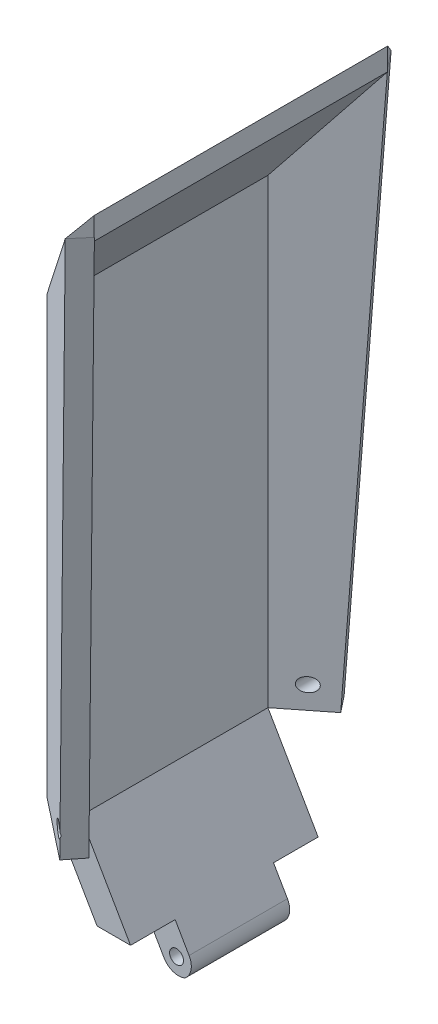
SolidWorks part; units mm, degrees
ref_plane "Front Plane" through (0, 0, 0) normal (0, 0, 1) x (1, 0, 0)
ref_plane "Top Plane" through (0, 0, 0) normal (0, 1, 0) x (1, 0, 0)
ref_plane "Right Plane" through (0, 0, 0) normal (1, 0, 0) x (0, 0, -1)
sketch "Sketch1" plane through (0, 0, 0) normal (0, 1, 0) x (1, 0, 0)
  line L4 (0, 0) -> (0, 16.82)
  line L5 (0, 16.82) -> (7.8551, 23.0085)
  line L6 (7.8551, 23.0085) -> (9.004, 21.5502)
  line L7 (9.004, 21.5502) -> (3, 16.82)
  line L8 (3, 16.82) -> (3, 0)
  line L9 (3, 0) -> (8.9971, -4.739)
  line L10 (8.9971, -4.739) -> (7.846, -6.2)
  line L11 (7.846, -6.2) -> (0, 0)
  point P2 (3, 16.82)
  point P3 (0, 0)
  point P11 (0, 0)
  point P12 (0, 0)
  dimension "D1" = 16.82
  dimension "D2" = 10
  dimension "D3" = 10
  dimension "D4" = 3
  dimension "D5" = 1.86
  dimension "D6" = 1.8566
extrude "Boss-Extrude1" add sketch "Sketch1" along normal blind 50
sketch "Sketch8" plane through (0, 0, 0) normal (0, 0, 1) x (1, 0, 0)
  line L0 (0, 0) -> (5.9985, -10.3896) construction
  line L2 (0, 50) -> (0, 0) construction
  line L3 (3, 0) -> (7, 0) construction
  point P8 (8.9971, 0)
  dimension "D1" = 150
  dimension "3.5" = 4
sketch "Sketch2" plane through (0, 0, 0) normal (-0.62, 0, 0.7846) x (0.7846, 0, 0.62)
  line L0 (11.46, 50) -> (0, 37)
  line L1 (0, 50) -> (0, 0) construction
  line L2 (0, 37) -> (0, 50)
  line L3 (0, 50) -> (11.46, 50)
  point P5 (10.6574, 50)
  point P8 (11.4137, 50)
  point P10 (0, 0)
  dimension "D1" = 13
  dimension "D2" = 11.46
extrude "Cut-Extrude1" cut sketch "Sketch2" along direction (0, 0, 1) on the side against the normal blind 30
sketch "Sketch5" plane through (-17.3103, 11.9728, 0) normal (-0.8224, 0.5688, 0) x (0, 0, 1)
  line L0 (0, 30.4304) -> (6.2, 44.2232)
  line L1 (6.2, 44.2232) -> (4.746, 46.2369)
  line L5 (-21.566, 46.2369) -> (-23.0085, 44.2391)
  line L6 (-23.0085, 44.2391) -> (-16.82, 30.4304)
  line L7 (-16.82, 30.4304) -> (0, 30.4304)
  line L8 (-21.566, 46.2369) -> (4.746, 46.2369)
  point P4 (0, 0)
  point P7 (-21.566, 46.2369)
extrude "Boss-Extrude2" add sketch "Sketch5" along direction (0, -1, 0) on the side of the normal blind 2 contours L8 L1 L0 L7 L6 L5
sketch "Sketch6" plane through (0, 0, 0) normal (-0.62, 0, 0.7846) x (0.7846, 0, 0.62)
  line L0 (10, 50.3438) -> (7, 0)
  line L2 (7, 0) -> (10, 0)
  line L3 (10, 0) -> (10, 50.3438)
  point P3 (6.2396, 0)
  point P5 (0, 0)
  dimension "D1" = 3
extrude "Cut-Extrude2" cut sketch "Sketch6" against normal blind 2
sketch "Sketch7" plane through (-8.1764, 0, -10.3783) normal (-0.6189, 0, -0.7855) x (-0.7855, 0, 0.6189)
  line L0 (-20.4091, 50.3569) -> (-20.4091, 0)
  line L1 (-20.4091, 0) -> (-17.4091, 0)
  line L3 (-17.4091, 0) -> (-20.4091, 50.3569)
  dimension "D1" = 3
extrude "Cut-Extrude3" cut sketch "Sketch7" against normal blind 2
sketch "Sketch9" plane through (0, 0, 0) normal (0, -1, 0) x (1, 0, 0)
  line L0 (0, 0) -> (3, 0)
  line L1 (3, 0) -> (3, -16.82)
  line L2 (3, -16.82) -> (0, -16.82)
  line L3 (0, -16.82) -> (0, 0)
extrude "Boss-Extrude3" add sketch "Sketch9" along direction (0.5, -0.866, 0) on the side of the normal blind 13
sketch "Sketch10" plane through (0, 0, 0) normal (-0.866, -0.5, 0) x (0, 0, 1)
  line L0 (-16.82, -9) -> (-12.82, -9)
  line L1 (-16.82, -13) -> (-16.82, 0) construction
  line L2 (-12.82, -9) -> (-12.82, -13)
  line L3 (0, -13) -> (-16.82, -13) construction
  line L4 (-12.82, -13) -> (-16.82, -13)
  line L5 (-16.82, -13) -> (-16.82, -9)
  line L6 (0, -9) -> (-4, -9)
  line L7 (0, -13) -> (0, 0) construction
  line L8 (-4, -9) -> (-4, -13)
  line L9 (-4, -13) -> (0, -13)
  line L10 (0, -13) -> (0, -9)
  dimension "D1" = 4
  dimension "D2" = 4
  dimension "D3" = 4
extrude "Cut-Extrude4" cut sketch "Sketch10" along direction (1, 0, 0) on the side against the normal blind 15
sketch "Sketch11" plane through (0, 0, -12.82) normal (0, 0, -1) x (-1, 0, 0)
  line L4 (-9.5, -11.2583) -> (-7.25, -12.5574)
  line L5 (-7.25, -12.5574) -> (-6.5, -11.2583)
  line L6 (-6.5, -11.2583) -> (-9.5, -11.2583)
  line L8 (-9.5, -11.2583) -> (-7.5, -7.7942) construction
  line L9 (-6.5, -11.2583) -> (-4.5, -7.7942) construction
  point P3 (-8.1953, -14.1079)
extrude "Boss-Extrude4" add sketch "Sketch11" against normal up to surface (8.82 mm away) contours L4 L5 L6 up to face at (7, -9.5263, -4)
fillet "Fillet1" radius 1.5 2 edges at (9.5, -11.2583, -8.41) (7.25, -12.5574, -8.41)
sketch "Sketch12" plane through (0, 0, -4) normal (0, 0, 1) x (1, 0, 0)
  line L0 (8.75, -9.9593) -> (6.5, -11.2583) construction
  circle A0 centre (7.625, -10.6088) radius 0.625
  point P6 (0, 0)
  point P7 (0, 0)
  point P8 (7.625, -10.6088)
  dimension "D1" = 1.25
extrude "Cut-Extrude5" cut sketch "Sketch12" against normal through all
sketch "Sketch15" plane through (0, 0, 0) normal (0, 0, 1) x (1, 0, 0)
  line L0 (3, 0) -> (7, 0) construction
  circle A0 centre (5, 2) radius 0.625
  point P5 (5, 0)
  dimension "D1" = 1.25
  dimension "D2" = 2
  dimension "D3" = 2
extrude "Cut-Extrude7" cut sketch "Sketch15" against normal through all and the other way through all
equation "\"8.5.000000mm\"=9"
